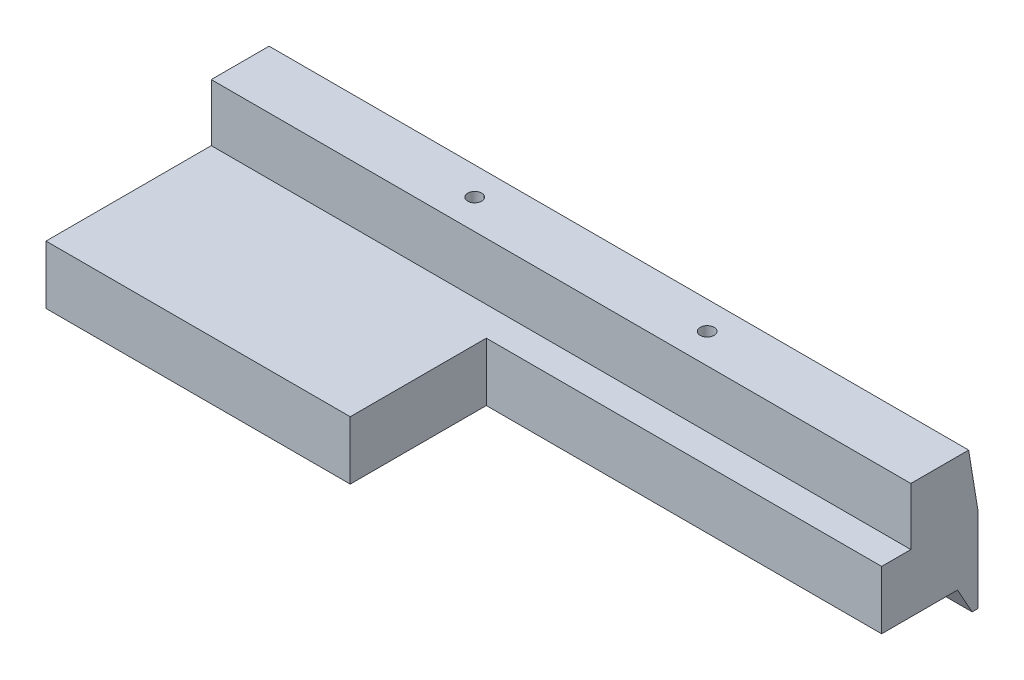
SolidWorks part; units mm, degrees
ref_plane "Płaszczyzna przednia" through (0, 0, 0) normal (0, 0, 1) x (1, 0, 0)
ref_plane "Płaszczyzna górna" through (0, 0, 0) normal (0, 1, 0) x (1, 0, 0)
ref_plane "Płaszczyzna prawa" through (0, 0, 0) normal (1, 0, 0) x (0, 0, -1)
sketch "Szkic1" plane through (0, 0, 0) normal (0, 0, 1) x (1, 0, 0)
  line L1 (-58.3066, 32.0248) -> (61.4934, 32.0248)
  line L2 (-58.3066, 32.0248) -> (-58.3066, 22.0248)
  line L3 (-58.3066, 22.0248) -> (61.4934, 22.0248)
  line L4 (61.4934, 32.0248) -> (61.4934, 22.0248)
  dimension "D1" = 119.8
  dimension "D2" = 10
extrude "Dodanie-wyciągnięcie2" add sketch "Szkic1" along normal blind 38.3 contours L2 L3 L4 L1
sketch "Szkic21" plane through (0, 32.0248, 0) normal (0, 1, 0) x (1, 0, 0)
  line L0 (61.4934, -38.3) -> (61.4934, 0) construction
  line L1 (-58.3066, 0) -> (61.4934, 0)
  line L2 (-58.3066, 0) -> (-58.3066, -10)
  line L3 (-58.3066, -10) -> (61.4934, -10)
  line L4 (61.4934, 0) -> (61.4934, -10)
extrude "Dodanie-wyciągnięcie3" add sketch "Szkic21" along normal blind 9.8
sketch "Szkic22" plane through (0, 22.0248, 0) normal (0, -1, 0) x (1, 0, 0)
  line L0 (-58.3066, 4.88) -> (-18.3066, 4.88) construction
  line L1 (-58.3066, 38.3) -> (-58.3066, 0) construction
  line L2 (-18.3066, 4.88) -> (21.4934, 4.88) construction
  line L3 (21.4934, 4.88) -> (61.4934, 4.88) construction
  line L4 (61.4934, 38.3) -> (61.4934, 0) construction
  line L5 (1.9729, 4.88) -> (1.9729, 0) construction
  line L6 (-58.3066, 0) -> (61.4934, 0) construction
hole_wizard "Pogłębienie walcowe pod M2 wkręt do części metalowych z łbem stożkowym ściętym2" positions "Szkic23" profile "Szkic24" counterbore size "M2" standard "Ansi Metric" end condition through all
sketch "Szkic23" plane through (0, 22.0248, 0) normal (0, -1, 0) x (-1, 0, 0)
  point P0 (-21.4934, -4.88)
  point P3 (18.3066, -4.88)
sketch "Szkic24" plane through (21.4934, 22.0248, 4.88) normal (1, 0, 0) x (0, 0, -1)
  line L0 (0, 0) -> (0, 19.8)
  line L1 (0, 19.8) -> (1.2, 19.8)
  line L3 (1.2, 19.8) -> (1.2, 1.6)
  line L4 (1.2, 1.6) -> (2.5, 1.6)
  line L5 (2.5, 1.6) -> (2.5, 0)
  line L7 (2.5, 0) -> (0, 0)
  line L11 (0, -6.35) -> (0, 107.95) construction
  dimension "Średnica otworu na wylot" = 2.4
  dimension "Głębokość otworu na wylot" = 19.8
  dimension "Średnica pogłębienia walcowego" = 5
  dimension "Głębokość pogłębienia walcowego" = 1.6
sketch "Szkic28" plane through (0, 22.0248, 0) normal (0, -1, 0) x (1, 0, 0)
  line L0 (36.4934, 0) -> (36.4934, 23.3) construction
  line L1 (-58.3066, 0) -> (61.4934, 0) construction
  line L2 (36.4934, 23.3) -> (61.4934, 23.3) construction
  line L3 (61.4934, 38.3) -> (61.4934, 0) construction
  line L4 (-58.3066, 38.3) -> (61.4934, 38.3) construction
  circle A0 centre (36.4934, 23.3) radius 11.1
  dimension "D1" = 15
extrude "Wytnij-wyciągnięcie1" cut sketch "Szkic28" against normal blind 7.2
sketch "Szkic31" plane through (61.4934, 0, 0) normal (1, 0, 0) x (0, 0, -1)
  line L0 (-10, 32.0248) -> (-10, 71.9248)
  line L2 (0, 41.2325) -> (0, 32.0248)
  line L6 (0, 41.8248) -> (0, 22.0248) construction
  line L8 (0, 32.0248) -> (1.5, 32.0248)
  line L10 (-10, 32.0248) -> (1.5, 32.0248)
  line L12 (-10, 71.9248) -> (-5, 71.9248)
  line L13 (-5, 71.9248) -> (1.5, 32.0248)
  line L14 (-0.4105, 43.7521) -> (0.2752, 39.543)
  line L15 (0.2752, 39.543) -> (3.3905, 40.0505)
  line L16 (3.3905, 40.0505) -> (-0.4105, 43.7521)
  line M5 (0, 22.0248) -> (0, 41.8248)
  line M6 (0, 41.8248) -> (-10, 41.8248)
extrude "Wytnij-wyciągnięcie4" cut sketch "Szkic31" against normal blind 124.8 contours L13 M6 M5 region at (61.4934, 41.6274, 0.0322)
extrude "Dodanie-wyciągnięcie5" add sketch "Szkic31<5>" against normal blind 119.8 contours L13 L8 M5 region at (61.4934, 35.0941, -0.5)
sketch "Szkic31<5>" plane through (61.4934, 0, 0) normal (1, 0, 0) x (0, 0, -1) same geometry as "Szkic31"
sketch "Szkic34" plane through (0, 0, 0) normal (0, 0, -1) x (-1, 0, 0)
  line L1 (-61.4934, 32.0248) -> (58.3066, 32.0248)
  line L2 (-61.4934, 32.0248) -> (-61.4934, 22.0248)
  line L3 (-61.4934, 22.0248) -> (58.3066, 22.0248)
  line L4 (58.3066, 32.0248) -> (58.3066, 22.0248)
extrude "Dodanie-wyciągnięcie6" add sketch "Szkic34" along normal blind 1.5
sketch "Szkic53" plane through (0, 0, 38.3) normal (0, 0, 1) x (1, 0, 0)
  line L1 (9.3934, 32.0248) -> (-58.3066, 32.0248)
  line L2 (9.3934, 32.0248) -> (9.3934, 22.0248)
  line L3 (9.3934, 22.0248) -> (-58.3066, 22.0248)
  line L4 (-58.3066, 32.0248) -> (-58.3066, 22.0248)
extrude "Wytnij-wyciągnięcie5" cut sketch "Szkic53" against normal blind 23.3
sketch "Szkic54" plane through (61.4934, 0, 0) normal (1, 0, 0) x (0, 0, -1)
  line L0 (-2, 22.0248) -> (1.5, 22.0248)
  line L1 (1.5, 17.5248) -> (0.5, 17.5248)
  line L2 (-4.88, 22.0248) -> (0, 22.0248) construction
  line L3 (-38.3, 22.0248) -> (1.5, 22.0248) construction
  line L4 (1.5, 22.0248) -> (1.5, 17.5248)
  line L6 (0.5, 17.5248) -> (-2, 22.0248)
extrude "Dodanie-wyciągnięcie12" add sketch "Szkic54" against normal blind 119.8
mirror "Lustro1" about plane through (-58.3066, 32.0248, 38.3) normal (1, 0, 0) of bodies 145
delete or keep bodies "Obiekt-Usuń/zachowaj 1" type delete bodies bodies 145
sketch "Szkic55" plane through (0, 22.0248, 0) normal (0, -1, 0) x (1, 0, 0)
  line L0 (-58.3066, 8.5) -> (-83.3066, 8.5) construction
  line L1 (-58.3066, 15) -> (-58.3066, 2) construction
  line L2 (-83.3066, 8.5) -> (-108.3066, 8.5) construction
  circle A0 centre (-108.3066, 8.5) radius 5.1
  circle A1 centre (-70.8066, 8.5) radius 5.1
extrude "Wytnij-wyciągnięcie6" cut sketch "Szkic55" against normal blind 4.1
